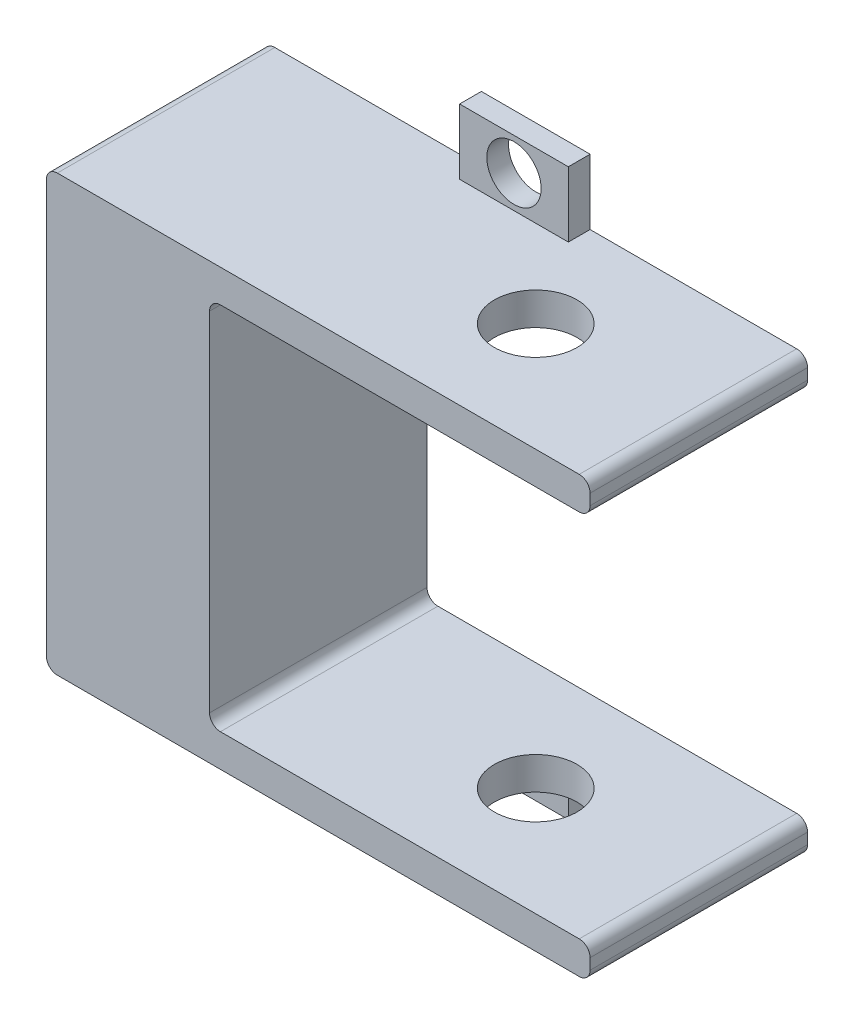
SolidWorks part; units mm, degrees
ref_plane "Front Plane" through (0, 0, 0) normal (0, 0, 1) x (1, 0, 0)
ref_plane "Top Plane" through (0, 0, 0) normal (0, 1, 0) x (1, 0, 0)
ref_plane "Right Plane" through (0, 0, 0) normal (1, 0, 0) x (0, 0, -1)
sketch "Sketch1" plane through (0, 0, 0) normal (0, 0, 1) x (1, 0, 0)
  line L1 (0, 0) -> (63.5, 0)
  line L2 (0, 0) -> (0, 50.8)
  line L3 (0, 50.8) -> (63.5, 50.8)
  line L4 (63.5, 0) -> (63.5, 50.8)
  dimension "D1" = 50.8
  dimension "D2" = 63.5
extrude "Boss-Extrude1" add sketch "Sketch1" along normal blind 25.4
sketch "Sketch3" plane through (0, 0, 0) normal (0, 0, -1) x (-1, 0, 0)
  line L0 (-63.5, 0) -> (-63.5, 50.8) construction
  line L1 (-63.5, 46.99) -> (-19.05, 46.99)
  line L2 (-63.5, 46.99) -> (-63.5, 3.81)
  line L3 (-63.5, 3.81) -> (-19.05, 3.81)
  line L4 (-19.05, 46.99) -> (-19.05, 3.81)
  line L9 (0, 0) -> (-63.5, 0) construction
  line L10 (-63.5, 50.8) -> (0, 50.8) construction
  dimension "D1" = 3.81
  dimension "D2" = 3.81
  dimension "D3" = 44.45
extrude "Cut-Extrude1" cut sketch "Sketch3" against normal blind 38.1
sketch "Sketch5" plane through (0, 0, 0) normal (0, -1, 0) x (1, 0, 0)
  line L0 (0, 0) -> (63.5, 0) construction
  circle A0 centre (44.45, 12.7) radius 4.826
  dimension "D1" = 9.652
  dimension "D2" = 12.7
  dimension "D3" = 19.05
extrude "Cut-Extrude2" cut sketch "Sketch5" against normal blind 76.2
fillet "Fillet3" radius 1.27 8 edges at (0, 50.8, 12.7) (0, 0, 12.7) (19.05, 3.81, 12.7) (19.05, 46.99, 12.7) (63.5, 3.81, 12.7) (63.5, 50.8, 12.7) (63.5, 46.99, 12.7) (63.5, 0, 12.7)
sketch "Sketch6" plane through (0, 50.8, 0) normal (0, 1, 0) x (1, 0, 0)
  line L5 (1.27, -25.4) -> (62.23, -25.4) construction
  line L6 (1.27, -22.86) -> (25.4, -22.86) construction
  line L7 (25.4, -25.4) -> (38.1, -25.4)
  line L8 (25.4, -25.4) -> (25.4, -22.86)
  line L9 (25.4, -22.86) -> (38.1, -22.86)
  line L10 (38.1, -25.4) -> (38.1, -22.86)
  line L11 (1.27, 0) -> (1.27, -25.4) construction
  line L12 (1.27, 0) -> (62.23, 0) construction
  dimension "D1" = 2.54
  dimension "D2" = 12.7
  dimension "D3" = 24.13
  dimension "D4" = 60.96
sketch "Sketch7" plane through (0, 0, 0) normal (0, -1, 0) x (1, 0, 0)
  line L0 (62.23, 22.86) -> (38.1, 22.86) construction
  line L1 (62.23, 0) -> (62.23, 25.4) construction
  line L2 (1.27, 25.4) -> (62.23, 25.4) construction
  line L3 (38.1, 22.86) -> (25.4, 22.86)
  line L4 (38.1, 22.86) -> (38.1, 25.4)
  line L5 (38.1, 25.4) -> (25.4, 25.4)
  line L6 (25.4, 22.86) -> (25.4, 25.4)
  dimension "D1" = 24.13
  dimension "D2" = 12.7
  dimension "D3" = 2.54
sketch "Sketch10" plane through (0, 0, 0) normal (0, -1, 0) x (1, 0, 0)
  line L0 (62.23, 2.54) -> (38.1, 2.54) construction
  line L1 (62.23, 0) -> (62.23, 25.4) construction
  line L2 (1.27, 0) -> (62.23, 0) construction
  line L3 (38.1, 2.54) -> (25.4, 2.54)
  line L4 (38.1, 2.54) -> (38.1, 0)
  line L5 (38.1, 0) -> (25.4, 0)
  line L6 (25.4, 2.54) -> (25.4, 0)
  dimension "D1" = 24.13
  dimension "D2" = 12.7
  dimension "D3" = 2.54
extrude "Boss-Extrude4" add sketch "Sketch10" along normal blind 7.62
sketch "Sketch11" plane through (0, 50.8, 0) normal (0, 1, 0) x (1, 0, 0)
  line L0 (1.27, -2.54) -> (25.4, -2.54) construction
  line L1 (1.27, 0) -> (1.27, -25.4) construction
  line L2 (62.23, 0) -> (1.27, 0) construction
  line L3 (25.4, -2.54) -> (38.1, -2.54)
  line L4 (25.4, -2.54) -> (25.4, 0)
  line L5 (25.4, 0) -> (38.1, 0)
  line L6 (38.1, -2.54) -> (38.1, 0)
  dimension "D1" = 24.13
  dimension "D2" = 12.7
  dimension "D3" = 2.54
extrude "Boss-Extrude5" add sketch "Sketch11" along normal blind 7.62
sketch "Sketch12" plane through (0, 0, 2.54) normal (0, 0, 1) x (1, 0, 0)
  line L0 (25.4, 54.61) -> (38.1, 54.61) construction
  line L1 (25.4, 58.42) -> (25.4, 50.8) construction
  line L2 (38.1, 58.42) -> (38.1, 50.8) construction
  line L3 (25.4, -3.81) -> (38.1, -3.81) construction
  line L4 (25.4, -7.62) -> (25.4, 0) construction
  line L5 (38.1, -7.62) -> (38.1, 0) construction
  circle A0 centre (31.75, 54.61) radius 3.175
  circle A1 centre (31.75, -3.81) radius 3.175
  dimension "D1" = 6.35
  dimension "D2" = 6.35
extrude "Cut-Extrude5" cut sketch "Sketch12" against normal up to next
sketch "Sketch13" plane through (0, 0, 0) normal (0, 0, -1) x (-1, 0, 0)
  line L0 (-19.05, 25.4) -> (0, 25.4) construction
  line L1 (-19.05, 5.08) -> (-19.05, 45.72) construction
  line L2 (0, 49.53) -> (0, 1.27) construction
  line L3 (-9.525, 50.8) -> (-9.525, 0) construction
  line L4 (-1.27, 50.8) -> (-62.23, 50.8) construction
  line L5 (-1.27, 0) -> (-25.4, 0) construction
  line L7 (-12.065, 27.94) -> (-6.985, 27.94)
  line L8 (-12.065, 27.94) -> (-12.065, 22.86)
  line L9 (-12.065, 22.86) -> (-6.985, 22.86)
  line L10 (-6.985, 27.94) -> (-6.985, 22.86)
  line L11 (-12.065, 27.94) -> (-6.985, 22.86) construction
  line L12 (-12.065, 22.86) -> (-6.985, 27.94) construction
  point P12 (-9.525, 25.4)
  dimension "D1" = 5.08
  dimension "D2" = 5.08
extrude "Boss-Extrude6" add sketch "Sketch13" along normal blind 6.35
sketch "Sketch14" plane through (12.065, 0, 0) normal (1, 0, 0) x (0, 0, -1)
  line L0 (6.35, 27.94) -> (0, 27.94) construction
  line L1 (6.35, 22.86) -> (3.81, 22.86)
  line L2 (6.35, 22.86) -> (6.35, 27.94)
  line L3 (6.35, 27.94) -> (3.81, 27.94)
  line L4 (3.81, 22.86) -> (3.81, 27.94)
  dimension "D1" = 2.54
sketch "Sketch15" plane through (12.065, 0, 0) normal (1, 0, 0) x (0, 0, -1)
  line L0 (3.175, 22.86) -> (3.175, 27.94) construction
  line L1 (6.35, 22.86) -> (0, 22.86) construction
  line L2 (6.35, 27.94) -> (0, 27.94) construction
  circle A0 centre (3.175, 25.4) radius 1.905
  dimension "D1" = 3.81
extrude "Cut-Extrude6" cut sketch "Sketch15" against normal up to next
fillet "Fillet5" radius 2.54 2 edges at (9.525, 27.94, -6.35) (9.525, 22.86, -6.35)
